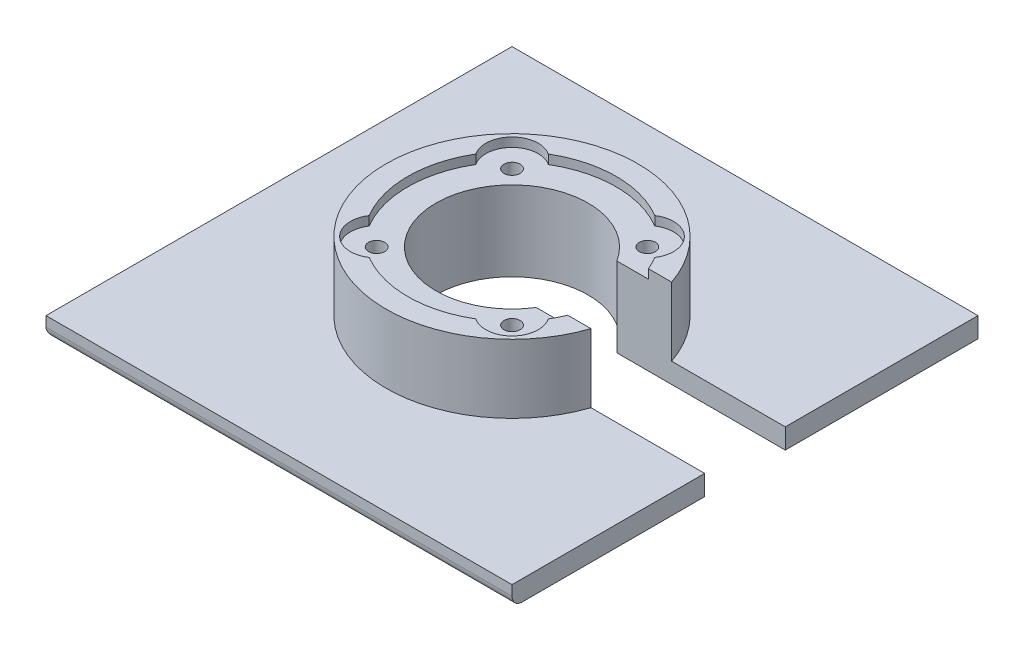
SolidWorks part; units mm, degrees
ref_plane "Front Plane" through (0, 0, 0) normal (0, 0, 1) x (1, 0, 0)
ref_plane "Top Plane" through (0, 0, 0) normal (0, 1, 0) x (1, 0, 0)
ref_plane "Right Plane" through (0, 0, 0) normal (1, 0, 0) x (0, 0, -1)
sketch "Sketch3" plane through (0, 0, 0) normal (0, 1, 0) x (1, 0, 0)
  circle A0 centre (0, 0) radius 7.55
  circle A1 centre (0, 0) radius 12.5
  dimension "D1" = 15.1
  dimension "D2" = 25
extrude "Boss-Extrude2" add sketch "Sketch3" along normal blind 8.8
sketch "Sketch4" plane through (0, 8.8, 0) normal (0, 1, 0) x (1, 0, 0)
  line L0 (6.4033, 4) -> (6.4033, -4)
  line L1 (6.4033, -4) -> (13.2817, -4)
  line L2 (13.2817, -4) -> (13.2817, 4)
  line L3 (13.2817, 4) -> (6.4033, 4)
  circle A0 centre (0, 0) radius 7.55 construction
  point P0 (0, 0)
  point P1 (6.4033, 4)
  point P3 (6.4033, -4)
  dimension "D1" = 4
extrude "Cut-Extrude2" cut sketch "Sketch4" against normal blind 8.8
sketch "Sketch5" plane through (0, 8.8, 0) normal (0, 1, 0) x (1, 0, 0)
  line L0 (0, 0) -> (17.4279, 0) construction
  line L1 (0, 0) -> (-11.2462, -11.2462) construction
  line L2 (0, 0) -> (-11.0539, 11.0539) construction
  point P0 (0, 0)
  point P1 (-6.715, 6.72)
  point P3 (-6.715, -6.72)
  point P9 (6.72, -6.715)
  point P10 (6.72, 6.715)
  dimension "D1" = 6.72
  dimension "D2" = 9.5
  dimension "D3" = 6.72
  dimension "D4" = 9.5
sketch "Sketch6" plane through (0, 8.8, 0) normal (0, 1, 0) x (1, 0, 0)
  line L0 (0, 0) -> (-11.2462, -11.2462) construction
  line L1 (0, 0) -> (-11.0539, 11.0539) construction
  line L2 (0, 0) -> (17.4279, 0) construction
  point P0 (5.2883, -8.8853)
  point P9 (-8.8853, 5.2883)
  point P12 (5.2883, 8.8853)
  point P14 (8.8893, -5.2817)
  point P15 (-5.2817, 8.8893)
  point P16 (8.8893, 5.2817)
  point P17 (-5.2817, -8.8893)
  point P18 (-8.8853, -5.2883)
  dimension "D1" = 2.6
  dimension "D2" = 10.34
  dimension "D3" = 2.6
  dimension "D4" = 10.34
sketch "Sketch8" plane through (0, 8.8, 0) normal (0, 1, 0) x (1, 0, 0)
  circle A0 centre (0, 0) radius 10.34
extrude "Cut-Extrude5" cut sketch "Sketch8" against normal blind 0.9
hole_wizard "Tap Drill for M2x0.4 Tap1" positions "3DSketch1" profile "Sketch10" hole size "M2x0.4" standard "ANSI Metric" end condition through all
sketch3d "3DSketch1"
  point P0 (6.72, 8.8, 6.715)
  point P3 (-6.715, 8.8, 6.72)
  point P6 (-6.715, 8.8, -6.72)
  point P9 (6.72, 8.8, -6.715)
sketch "Sketch10" plane through (6.72, 8.8, 6.715) normal (1, 0, 0) x (0, 0, 1)
  line L0 (0, 0) -> (0, 8.8)
  line L1 (0, 8.8) -> (0.8, 8.8)
  line L2 (0.8, 8.8) -> (0.8, 0)
  line L5 (0.8, 0) -> (0, 0)
  line L11 (0, -6.35) -> (0, 107.95) construction
  dimension "Thru Hole Dia." = 1.6
  dimension "Thru Hole Depth" = 8.8
sketch "Sketch11" plane through (0, 8.8, 0) normal (0, 1, 0) x (1, 0, 0)
  line L0 (8.8893, 5.2817) -> (5.2883, 8.8853)
  line L1 (8.8893, -5.2817) -> (5.2883, -8.8853)
  line L2 (-5.2817, -8.8893) -> (-8.8853, -5.2883)
  line L3 (-5.2817, 8.8893) -> (-8.8853, 5.2883)
  arc A0 (5.2883, -8.8853) -> (8.8893, -5.2817) centre (6.72, -6.715) ccw
  arc A1 (9.535, 4) -> (9.535, -4) centre (0, 0) ccw construction
  arc A2 (8.8893, 5.2817) -> (5.2883, 8.8853) centre (6.72, 6.715) ccw
  arc A3 (-5.2817, 8.8893) -> (-8.8853, 5.2883) centre (-6.715, 6.72) ccw
  arc A4 (-8.8853, -5.2883) -> (-5.2817, -8.8893) centre (-6.715, -6.72) ccw
extrude "Cut-Extrude6" cut sketch "Sketch11" against normal blind 0.9
sketch "Sketch12" plane through (0, 0, 0) normal (0, -1, 0) x (1, 0, 0)
  line L0 (0, 0) -> (17.7684, 0) construction
  line L1 (0, 0) -> (0, 18.0241) construction
  line L2 (23.125, -23.125) -> (-23.125, -23.125)
  line L3 (-23.125, -23.125) -> (-23.125, 23.125)
  line L4 (-23.125, 23.125) -> (23.125, 23.125)
  line L9 (6.4033, 4) -> (23.125, 4)
  line L11 (23.125, -4) -> (6.4033, -4)
  line L13 (23.125, -23.125) -> (23.125, -4)
  line L14 (23.125, 23.125) -> (23.125, 4)
  arc A0 (6.4033, -4) -> (6.4033, 4) centre (0, 0) cw
  arc A1 (6.4033, 4) -> (6.4033, -4) centre (0, 0) ccw construction
  point P0 (23.125, -23.125)
  point P4 (23.125, 23.125)
  point P5 (-23.125, 23.125)
  point P7 (-23.125, -23.125)
  dimension "D1" = 23.125
  dimension "D2" = 23.125
extrude "Boss-Extrude4" add sketch "Sketch12" against normal blind 2
fillet "Fillet2" radius 1 2 edges at (-23.125, 0, 0) (0, 0, 23.125)
